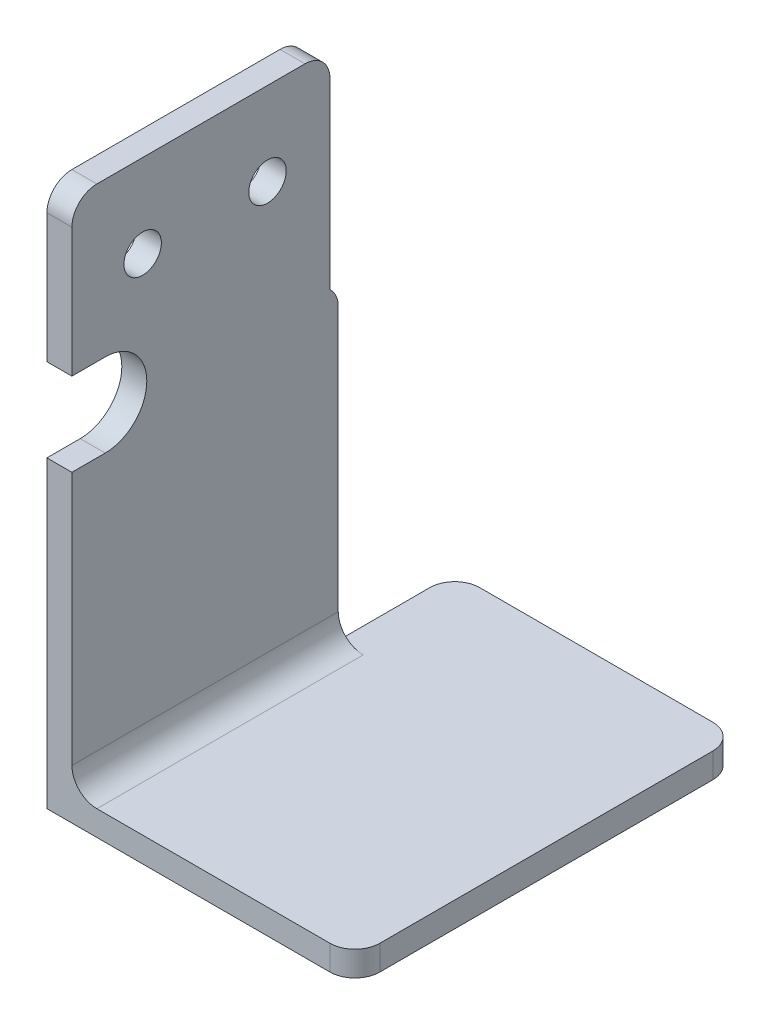
SolidWorks part; units mm, degrees
ref_plane "Front Plane" through (0, 0, 0) normal (0, 0, 1) x (1, 0, 0)
ref_plane "Top Plane" through (0, 0, 0) normal (0, 1, 0) x (1, 0, 0)
ref_plane "Right Plane" through (0, 0, 0) normal (1, 0, 0) x (0, 0, -1)
sketch "Sketch1" plane through (0, 0, 0) normal (0, 0, 1) x (1, 0, 0)
  line L0 (0, 0) -> (0, 65)
  line L1 (0, 65) -> (3, 65)
  line L2 (3, 65) -> (3, 3)
  line L3 (3, 3) -> (37, 3)
  line L4 (37, 3) -> (37, 0)
  line L5 (37, 0) -> (0, 0)
  dimension "D1" = 3
  dimension "D2" = 3
  dimension "D3" = 65
  dimension "D4" = 37
extrude "Boss-Extrude1" add sketch "Sketch1" along normal blind 46
sketch "Sketch2" plane through (0, 0, 0) normal (-1, 0, 0) x (0, 0, 1)
  line L0 (46, 0) -> (0, 0) construction
  line L1 (0, 65) -> (14, 65)
  line L2 (0, 65) -> (0, 0)
  line L3 (0, 0) -> (14, 0)
  line L4 (14, 65) -> (14, 0) construction
  line L5 (0, 65) -> (14, 0) construction
  line L6 (0, 0) -> (14, 65) construction
  line L7 (14, 65) -> (46, 65) construction
  line L8 (14, 0) -> (14, 40)
  line L13 (42, 65) -> (42, 41.5) construction
  line L14 (42, 41.5) -> (46, 41.5) construction
  line L15 (14, 40) -> (15, 40)
  line L16 (15, 40) -> (15, 65)
  line L17 (15, 65) -> (14, 65)
  line L18 (46, 65) -> (46, 0) construction
  line L19 (42, 46.5) -> (46, 46.5)
  line L20 (46, 46.5) -> (46, 36.5)
  line L21 (46, 36.5) -> (42, 36.5)
  circle A0 centre (42, 41.5) radius 5 construction
  arc A1 (42, 36.5) -> (42, 46.5) centre (42, 41.5) cw
  point P4 (7, 32.5)
  dimension "D2" = 10
  dimension "D1" = 32
  dimension "D3" = 23.5
  dimension "D4" = 25
  dimension "D5" = 1
  dimension "D6" = 4
extrude "Cut-Extrude1" cut sketch "Sketch2" against normal up to vertex (3 mm away) up to point (3, 3, 0)
sketch "Sketch3" plane through (3, 0, 0) normal (1, 0, 0) x (0, 0, -1)
  line L0 (-14, 40) -> (-14, 65) construction
  line L1 (-14, 65) -> (-46, 65) construction
  line L3 (-30, 65) -> (-30, 55) construction
  line L4 (-37.5, 55) -> (-22.5, 55) construction
  circle A0 centre (-37.5, 55) radius 2.25
  circle A1 centre (-22.5, 55) radius 2.25
  point P10 (-30, 55)
  dimension "D2" = 4.5
  dimension "D1" = 15
  dimension "D3" = 10
extrude "Cut-Extrude2" cut sketch "Sketch3" against normal blind 46
fillet "Fillet1" radius 3 7 edges at (1.5, 40, 14) (37, 1.5, 46) (37, 1.5, 0) (3, 1.5, 0) (1.5, 65, 46) (1.5, 65, 15) (3, 3, 30)
